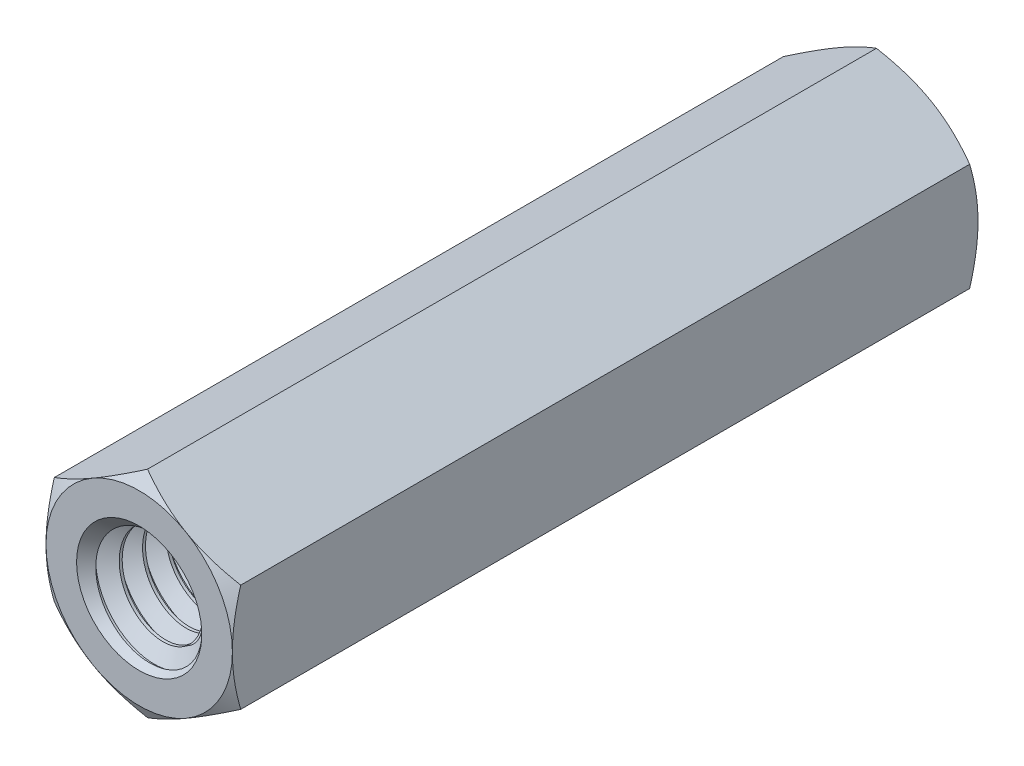
SolidWorks part; units mm, degrees
material "6061 Alloy"
ref_plane "Front Plane" through (0, 0, 0) normal (0, 0, 1) x (1, 0, 0)
ref_plane "Top Plane" through (0, 0, 0) normal (0, 1, 0) x (1, 0, 0)
ref_plane "Right Plane" through (0, 0, 0) normal (1, 0, 0) x (0, 0, -1)
sketch "Sketch3" plane through (0, 0, 0) normal (1, 0, 0) x (0, 0, -1)
  line L0 (-12.7, 0) -> (12.7, 0) construction
  line L1 (0, 3.175) -> (0, -3.175) construction
  line L2 (-12.7, 2.0828) -> (-12.7, -2.0828) construction
  point P2 (-3.175, 0)
  point P3 (3.175, 0)
  dimension "Length" = 25.4
  dimension "Min Thread Length" = 15.875
  dimension "D1" = 15.875
  dimension "Thread Dia" = 4.1656
  dimension "Hex" = 6.35
sketch "Sketch1" plane through (0, 0, 0) normal (0, 0, 1) x (1, 0, 0)
  line L1 (0, 3.6662) -> (-3.175, 1.8331)
  line L2 (-3.175, 1.8331) -> (-3.175, -1.8331)
  line L3 (-3.175, -1.8331) -> (0, -3.6662)
  line L4 (0, -3.6662) -> (3.175, -1.8331)
  line L5 (3.175, -1.8331) -> (3.175, 1.8331)
  line L6 (3.175, 1.8331) -> (0, 3.6662)
  circle A0 centre (0, 0) radius 3.175 construction
  circle A1 centre (0, 0) radius 2.0828
extrude "Extrude1" add sketch "Sketch1" along normal up to vertex (12.7 mm away) and the other way up to vertex (12.7 mm away) up to point (0, 0, 12.7) other way up to point (0, 0, -12.7)
sketch "Sketch11" plane through (0, 0, -12.7) normal (0, 0, -1) x (-1, 0, 0)
  circle A0 centre (0, 0) radius 2.0828 construction
  circle A1 centre (0, 0) radius 2.0828
curve "Helix/Spiral1" pitch 0.7937 height 26.1937 turns 33 parameters "Pitch"=0.7937
sketch "Sketch12" plane through (0, 0, 0) normal (1, 0, 0) x (0, 0, -1)
  line L0 (13.3945, 2.0828) -> (12.7, 2.0828)
  line L1 (13.3945, 2.0828) -> (13.0969, 1.5672)
  line L2 (13.0969, 1.5672) -> (12.9977, 1.5672)
  line L3 (12.9977, 1.5672) -> (12.7, 2.0828)
  line L4 (13.0473, 1.5672) -> (13.0473, 2.0828) construction
  line L5 (13.2457, 1.825) -> (12.8488, 1.825) construction
  dimension "D1" = 0.0992
  dimension "D2" = 0.3969
  dimension "D3" = 60
sweep "Sweep1" add profiles "Sketch12" path "Helix/Spiral1"
sketch "Sketch6" plane through (0, 0, -12.7) normal (0, 0, -1) x (-1, 0, 0)
  line L6 (0, 3.6662) -> (-3.175, 1.8331)
  line L7 (-3.175, 1.8331) -> (-3.175, -1.8331)
  line L8 (-3.175, -1.8331) -> (0, -3.6662)
  line L9 (0, -3.6662) -> (3.175, -1.8331)
  line L10 (3.175, -1.8331) -> (3.175, 1.8331)
  line L11 (3.175, 1.8331) -> (0, 3.6662)
  line L12 (0, 3.6662) -> (-3.175, 1.8331)
  line L13 (-3.175, 1.8331) -> (-3.175, -1.8331)
  line L14 (-3.175, -1.8331) -> (0, -3.6662)
  line L15 (0, -3.6662) -> (3.175, -1.8331)
  line L16 (3.175, -1.8331) -> (3.175, 1.8331)
  line L17 (3.175, 1.8331) -> (0, 3.6662)
  dimension "D1" = 0
extrude "Extrude2" cut sketch "Sketch6" along normal through all
sketch "Sketch7" plane through (0, 0, -12.7) normal (0, 0, -1) x (-1, 0, 0)
  circle A2 centre (0, 0) radius 2.1336
  circle A3 centre (0, 0) radius 2.1336
  dimension "D1" = 0.0508
extrude "Extrude3" cut sketch "Sketch7" against normal through all draft 43
sketch "Sketch8" plane through (0, 0, -12.7) normal (0, 0, -1) x (-1, 0, 0)
  circle A0 centre (0, 0) radius 3.175 construction
  circle A1 centre (0, 0) radius 3.175
extrude "Extrude4" cut sketch "Sketch8" against normal through all draft 60 flip side to cut
mirror "Mirror1" about plane through (0, 0, 0) normal (0, 0, 1) of "Extrude2", "Extrude3", "Extrude4"
sketch "Sketch9" [suppressed] plane through (0, 0, 0) normal (1, 0, 0) x (0, 0, -1)
  line L1 (-22.225, 3.2258) -> (22.225, 3.2258)
  line L2 (-22.225, 3.2258) -> (-22.225, 0)
  line L3 (-22.225, 0) -> (22.225, 0)
  line L4 (22.225, 3.2258) -> (22.225, 0)
  line L7 (-38.1, 0) -> (38.1, 0) construction
revolve "Revolve" [suppressed] add sketch "Sketch9" angle 360 about L0
sketch "Sketch10" [suppressed] plane through (0, 0, 0) normal (1, 0, 0) x (0, 0, -1)
  line L0 (38.1, 3.175) -> (22.225, 3.175)
  line L1 (-38.1, 3.175) -> (-22.225, 3.175)
  line L2 (22.225, 3.175) -> (22.225, -3.175)
  line L3 (-38.1, -3.2258) -> (-22.225, -3.2258)
  line L4 (-22.225, 3.175) -> (-22.225, -3.2258)
  line L5 (22.225, -3.175) -> (38.1, -3.175)
equation "\"D1@Sketch3\" = \"Min Thread Length@Sketch3\""
equation "\"D3@Helix/Spiral1\" = \"Length@Sketch3\"+\"Pitch@Helix/Spiral1\""
equation "\"D1@Sketch12\" = \"Pitch@Helix/Spiral1\"*.125"
equation "\"D2@Sketch12\" = \"Pitch@Helix/Spiral1\"*.5"
